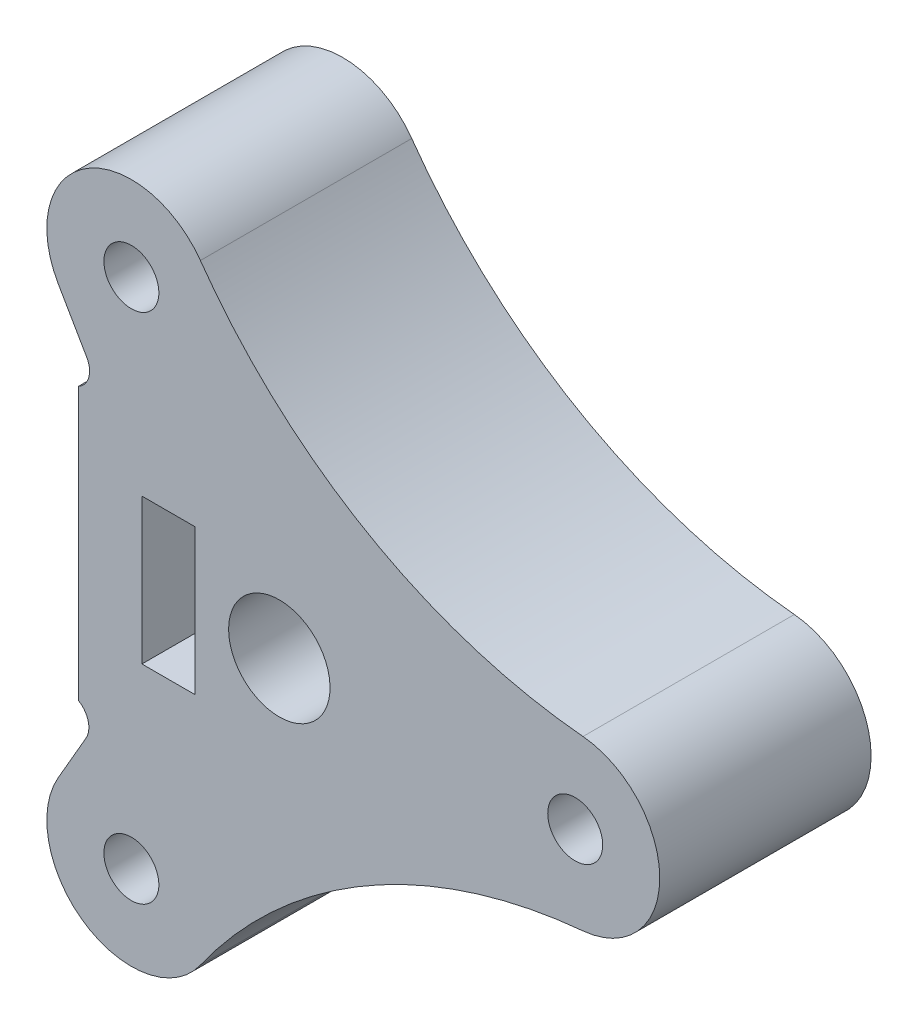
SolidWorks part; units mm, degrees
material "ABS PC"
ref_plane "Front Plane" through (0, 0, 0) normal (0, 0, 1) x (1, 0, 0)
ref_plane "Top Plane" through (0, 0, 0) normal (0, 1, 0) x (1, 0, 0)
ref_plane "Right Plane" through (0, 0, 0) normal (1, 0, 0) x (0, 0, -1)
other "Center of Mass"
sketch "Sketch1" plane through (0, 0, 0) normal (0, 0, 1) x (1, 0, 0)
  line L0 (-12.065, 8.128) -> (-1.27, 8.128)
  line L1 (-8.255, 4.318) -> (-5.08, 4.318)
  line L2 (-8.255, 4.318) -> (-8.255, -4.4196)
  line L3 (-8.255, -4.4196) -> (-5.08, -4.4196)
  line L4 (-5.08, 4.318) -> (-5.08, -4.4196)
  line L6 (-12.065, -8.2296) -> (-1.27, -8.2296)
  line L7 (-12.065, 8.128) -> (-12.065, -8.2296)
  line L8 (-1.27, 8.128) -> (3.4486, 4.5572)
  line L9 (-1.27, -8.2296) -> (3.7294, -4.3304)
  line L10 (-1.27, 8.128) -> (-1.27, -8.2296) construction
  circle A0 centre (0, 0) radius 3.048
  arc A1 (3.7294, -4.3304) -> (3.4486, 4.5572) centre (0, 0) ccw
  dimension "D1" = 6.096
  dimension "D2" = 11.43
  dimension "D6" = 5.08
  dimension "D3" = 8.7376
  dimension "D4" = 3.175
  dimension "D5" = 4.318
  dimension "D7" = 3.81
extrude "Boss-Extrude1" add sketch "Sketch1" along normal blind 17.78
sketch "Sketch4" plane through (0, 0, 0) normal (0, 0, -1) x (-1, 0, 0)
  circle A0 centre (0, 0) radius 28.575 construction
  dimension "D1" = 57.15
sketch "Sketch3" plane through (-5.08, 0, 0) normal (-1, 0, 0) x (0, 0, 1)
  line L0 (17.78, 4.318) -> (0, 4.318) construction
  line L1 (3.937, -4.4196) -> (13.843, -4.4196)
  line L2 (3.937, -4.4196) -> (3.937, 4.318)
  line L3 (3.937, 4.318) -> (13.843, 4.318)
  line L4 (13.843, -4.4196) -> (13.843, 4.318)
  line L5 (3.937, -4.4196) -> (13.843, 4.318) construction
  line L6 (3.937, 4.318) -> (13.843, -4.4196) construction
  line L8 (3.937, 4.318) -> (0, 4.318)
  line L9 (3.937, 4.318) -> (3.937, -4.4196)
  line L10 (3.937, -4.4196) -> (0, -4.4196)
  line L11 (0, 4.318) -> (0, -4.4196)
  point P0 (8.89, -0.0508)
  line M4 (0, 4.318) -> (0, -4.4196)
  line M5 (0, -4.4196) -> (17.78, -4.4196)
  line M7 (17.78, 4.318) -> (0, 4.318)
  dimension "D1" = 9.906
extrude "Boss-Extrude2" add sketch "Sketch3" along normal up to surface (3.175 mm away) contours L2 M5 M7 M4 region at (-5.08, -0.0508, 1.9685) up to face at (-8.255, -0.0508, 8.89)
sketch "Sketch5" plane through (0, 0, 0) normal (0, 0, -1) x (-1, 0, 0)
  line L0 (0, 0) -> (8.89, 15.3979) construction
  line L1 (-2.9329, 5.08) -> (4.4906, 17.9379)
  line L2 (8.6522, 4.826) -> (13.2894, 12.8579)
  line L3 (-2.9329, -5.08) -> (4.4906, -17.9379)
  line L4 (8.4175, -4.4196) -> (13.2894, -12.8579)
  line L5 (0, 0) -> (8.89, -15.3979) construction
  line L6 (-2.9329, 5.08) -> (-17.78, 5.08)
  line L7 (-2.9329, -5.08) -> (-17.78, -5.08)
  line L8 (0, 0) -> (-17.78, 0) construction
  line L9 (0, 0) -> (-28.575, 0) construction
  line L11 (8.6522, 4.826) -> (5.08, 4.826)
  line L13 (8.4175, -4.4196) -> (5.08, -4.4196)
  line L14 (5.08, 4.826) -> (5.08, -4.4196)
  arc A1 (13.2894, 12.8579) -> (4.4906, 17.9379) centre (8.89, 15.3979) ccw
  circle A2 centre (8.89, 15.3979) radius 1.651
  arc A4 (4.4906, -17.9379) -> (13.2894, -12.8579) centre (8.89, -15.3979) ccw
  circle A5 centre (8.89, -15.3979) radius 1.651
  arc A7 (-17.78, 5.08) -> (-17.78, -5.08) centre (-17.78, 0) ccw
  circle A8 centre (-17.78, 0) radius 1.651
  circle A9 centre (0, 0) radius 28.575 construction
  circle A12 centre (0, 0) radius 3.048
  point P3 (4.445, 7.699)
  point P13 (4.445, -7.699)
  point P21 (-8.89, 0)
  point P28 (0, 0)
  dimension "D2" = 5.08
  dimension "D3" = 3.302
  dimension "D1" = 17.78
  dimension "D5" = 0
  dimension "D4" = 3
extrude "Boss-Extrude3" add sketch "Sketch5" against normal blind 17.78
fillet "Fillet1" radius 31.75 2 edges at (2.9329, -5.08, 8.89) (2.9329, 5.08, 8.89)
fillet "Fillet2" radius 1.27 2 edges at (-10.5586, 8.128, 8.89) (-10.6172, -8.2296, 8.89)
sketch "Sketch2" plane through (-12.065, 0, 0) normal (-1, 0, 0) x (0, 0, 1)
  line L0 (0, -0.0508) -> (17.78, -0.0508) construction
  line L1 (0, 8.128) -> (0, -8.2296) construction
  line L2 (17.78, 8.128) -> (17.78, -8.2296) construction
  circle A0 centre (8.89, -0.0508) radius 2.159
  dimension "D1" = 4.318
extrude "Cut-Extrude2" cut sketch "Sketch2" against normal blind 12.7
sketch "Sketch7" plane through (-12.065, 0, 0) normal (-1, 0, 0) x (0, 0, 1)
  line L1 (2.54, -25.4508) -> (15.24, -25.4508)
  line L2 (2.54, -25.4508) -> (2.54, 25.3492)
  line L3 (2.54, 25.3492) -> (15.24, 25.3492)
  line L4 (15.24, -25.4508) -> (15.24, 25.3492)
  line L5 (2.54, -25.4508) -> (15.24, 25.3492) construction
  line L6 (2.54, 25.3492) -> (15.24, -25.4508) construction
  line L7 (-3.1594, -31.9833) -> (20.9394, -31.9833)
  line L8 (-3.1594, -31.9833) -> (-3.1594, 31.8817)
  line L9 (-3.1594, 31.8817) -> (20.9394, 31.8817)
  line L10 (20.9394, -31.9833) -> (20.9394, 31.8817)
  line L11 (-3.1594, -31.9833) -> (20.9394, 31.8817) construction
  line L12 (-3.1594, 31.8817) -> (20.9394, -31.9833) construction
  point P0 (8.89, -0.0508)
  point P6 (8.89, -0.0508)
  dimension "D1" = 12.7
  dimension "D2" = 50.8
extrude "Cut-Extrude3" cut sketch "Sketch7" against normal through all both and the other way through all
